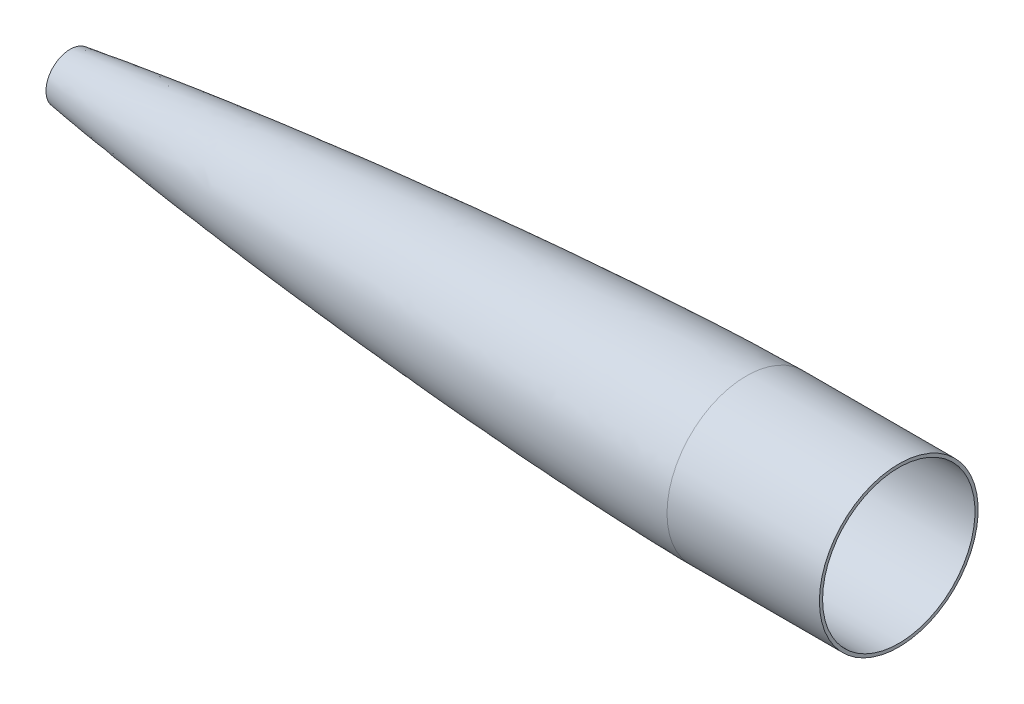
SolidWorks part; units mm, degrees
other "Markup1"
sketch "Sketch16" plane through (117.475, 79.375, -79.375) normal (-0.0459, 0.281, -0.9586) x (0.9922, 0.1242, -0.0111)
material "G10 Fiberglass"
ref_plane "Front Plane" through (0, 0, 0) normal (0, 0, 1) x (1, 0, 0)
ref_plane "Top Plane" through (0, 0, 0) normal (0, 1, 0) x (1, 0, 0)
ref_plane "Right Plane" through (0, 0, 0) normal (1, 0, 0) x (0, 0, -1)
sketch "Sketch1" plane through (0, 0, 0) normal (0, 1, 0) x (1, 0, 0)
  line L1 (0, 0) -> (793.75, 0)
  line L2 (793.75, 0) -> (793.75, 79.375)
  spline S0 degree 4 poles (0, 0) (0.0028, 0.0078) (0.0096, 0.0227) (0.0284, 0.0498) (0.0724, 0.0988) (0.1391, 0.1598) (0.2295, 0.2311) (0.3579, 0.3219) (0.5122, 0.4206) (0.6933, 0.5271) (0.9012, 0.641) (1.204, 0.7973) (1.6738, 1.0225) (2.4713, 1.3717) (3.8977, 1.9332) (6.468, 2.8305) (11.1915, 4.2735) (20.0573, 6.6167) (35.5284, 10.1233) (61.8137, 15.2483) (97.9042, 21.2946) (141.6495, 27.7549) (190.2981, 34.191) (239.0162, 40.0719) (287.7877, 45.4913) (336.602, 50.5093) (385.4525, 55.1611) (434.3344, 59.4688) (483.2447, 63.4427) (532.1808, 67.084) (581.1412, 70.3837) (630.1247, 73.3211) (673.0049, 75.541) (709.7734, 77.1509) (739.4239, 78.2178) (759.3843, 78.8014) (775.7823, 79.1676) (786.0492, 79.32) (791.183, 79.3686) (793.75, 79.375) knots 0 0 0 0 0 0.000041 0.000082 0.000164 0.000329 0.000493 0.000658 0.000951 0.001245 0.001545 0.001844 0.002657 0.003853 0.005902 0.009516 0.016281 0.028569 0.051794 0.088907 0.150314 0.211721 0.273128 0.334535 0.395942 0.457348 0.518755 0.580162 0.641569 0.702976 0.764383 0.825789 0.887196 0.9179 0.948603 0.974302 0.987151 1 1 1 1 1 construction
  spline S1 degree 4 poles (0, 0) (0.0028, 0.0078) (0.0096, 0.0227) (0.0284, 0.0498) (0.0724, 0.0988) (0.1391, 0.1598) (0.2295, 0.2311) (0.3579, 0.3219) (0.5122, 0.4206) (0.6933, 0.5271) (0.9012, 0.641) (1.204, 0.7973) (1.6738, 1.0225) (2.4713, 1.3717) (3.8977, 1.9332) (6.468, 2.8305) (11.1915, 4.2735) (20.0573, 6.6167) (35.5284, 10.1233) (61.8137, 15.2483) (97.9042, 21.2946) (141.6495, 27.7549) (190.2981, 34.191) (239.0162, 40.0719) (287.7877, 45.4913) (336.602, 50.5093) (385.4525, 55.1611) (434.3344, 59.4688) (483.2447, 63.4427) (532.1808, 67.084) (581.1412, 70.3837) (630.1247, 73.3211) (673.0049, 75.541) (709.7734, 77.1509) (739.4239, 78.2178) (759.3843, 78.8014) (775.7823, 79.1676) (786.0492, 79.32) (791.183, 79.3686) (793.75, 79.375) knots 0 0 0 0 0 0.000041 0.000082 0.000164 0.000329 0.000493 0.000658 0.000951 0.001245 0.001545 0.001844 0.002657 0.003853 0.005902 0.009516 0.016281 0.028569 0.051794 0.088907 0.150314 0.211721 0.273128 0.334535 0.395942 0.457348 0.518755 0.580162 0.641569 0.702976 0.764383 0.825789 0.887196 0.9179 0.948603 0.974302 0.987151 1 1 1 1 1
  dimension "D1" = 79.375
  dimension "D2" = 793.75
revolve "Revolve1" add sketch "Sketch1" angle 360 about L1
ref_plane "Plane1" through (0, 0, 76.2) normal (0, 0, 1) x (1, 0, 0)
sketch "Sketch5" plane through (0, 0, 0) normal (0, 1, 0) x (1, 0, 0)
  line L0 (793.75, 0) -> (-34.5199, 0) construction
sketch "Sketch7" [suppressed] plane through (0, 0, 0) normal (0, 0, 1) x (1, 0, 0)
  line L0 (228.6, -31.2846) -> (228.6, -364.3992)
  line L1 (76.2, 19.05) -> (76.2, -19.05) construction
  line L2 (238.76, -21.1246) -> (793.4316, -21.1246)
  line L3 (793.4316, -85.5566) -> (793.4316, 85.5566) construction
  arc A0 (238.76, -21.1246) -> (228.6, -31.2846) centre (238.76, -31.2846) ccw
  dimension "D2" = 10.16
  dimension "D1" = 152.4
ref_plane "Plane2" through (0, -76.2, 0) normal (0, 1, 0) x (1, 0, 0)
sketch "Sketch8" [suppressed] plane through (0, -76.2, 0) normal (0, 1, 0) x (1, 0, 0)
  circle A0 centre (229.0372, 0) radius 3.175
ref_plane "Plane3" through (117.475, 0, 0) normal (1, 0, 0) x (0, 0, -1)
shell "Shell1" thickness 3.175 removed face at (793.75, 0, 79.375)
sketch "Sketch12" plane through (117.475, 0, 0) normal (1, 0, 0) x (0, 0, -1)
  circle A0 centre (0, 0) radius 101.6
  dimension "D1" = 203.2
extrude "Cut-Extrude6" cut sketch "Sketch12" against normal through all
sketch "Sketch10" [suppressed] plane through (794.0738, 0, 0) normal (1, 0, 0) x (0, 0, -1)
  circle A0 centre (0, 0) radius 76.2
  dimension "D1" = 152.4
sketch "Sketch13" plane through (793.75, 0, 0) normal (1, 0, 0) x (0, 0, -1)
  circle A0 centre (0, 0) radius 79.375 construction
  circle A1 centre (0, 0) radius 79.375
  circle A2 centre (0, 0) radius 76.2
  dimension "D1" = 152.4
extrude "Boss-Extrude1" add sketch "Sketch13" along normal blind 152.4
